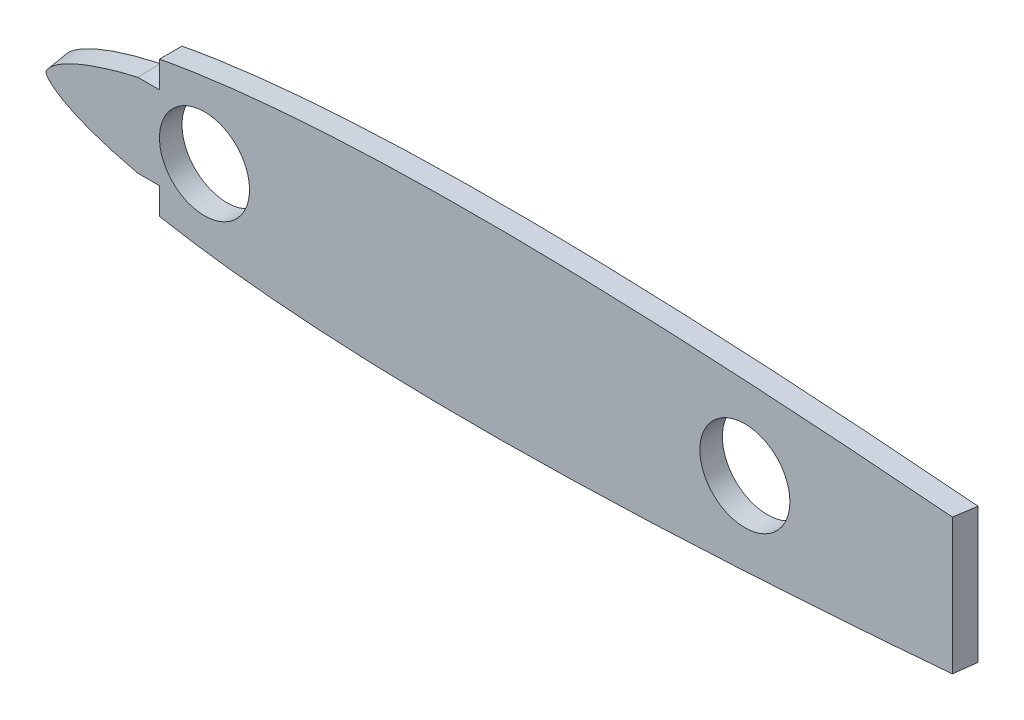
SolidWorks part; units mm, degrees
material "Balsa"
ref_plane "Front Plane" through (0, 0, 0) normal (0, 0, 1) x (1, 0, 0)
ref_plane "Top Plane" through (0, 0, 0) normal (0, 1, 0) x (1, 0, 0)
ref_plane "Right Plane" through (0, 0, 0) normal (1, 0, 0) x (0, 0, -1)
curve "Curve6"
  spline degree 3 poles (214.2507, -0.3619, 0) (214.2507, 0.3619, 0) (213.529, 0.2735, 0) (212.6145, 0.5309, 0) (210.9374, 0.6901, 0) (208.6782, 1.0315, 0) (205.7679, 1.4126, 0) (202.2583, 1.8823, 0) (198.1585, 2.4132, 0) (193.4982, 3.0043, 0) (188.3046, 3.6452, 0) (182.6103, 4.3273, 0) (176.4501, 5.042, 0) (169.8621, 5.7798, 0) (162.8869, 6.5315, 0) (155.5675, 7.2878, 0) (147.9491, 8.039, 0) (140.0787, 8.7745, 0) (132.0046, 9.4847, 0) (123.7769, 10.1577, 0) (115.4459, 10.7824, 0) (107.0633, 11.3474, 0) (98.6805, 11.8408, 0) (90.3493, 12.2502, 0) (82.1211, 12.5645, 0) (74.0464, 12.7737, 0) (66.175, 12.8673, 0) (58.5554, 12.8381, 0) (51.2345, 12.6804, 0) (44.2574, 12.3902, 0) (37.667, 11.9666, 0) (31.5038, 11.4111, 0) (25.8056, 10.7279, 0) (20.6071, 9.9229, 0) (15.9397, 9.0044, 0) (11.8309, 7.9828, 0) (8.304, 6.8681, 0) (5.3769, 5.6708, 0) (3.0589, 4.3988, 0) (1.3536, 3.0497, 0) (0.2614, 1.5908, 0) (-0.1218, 0, 0) (0.2614, -1.5908, 0) (1.3536, -3.0497, 0) (3.0589, -4.3988, 0) (5.3769, -5.6708, 0) (8.304, -6.8681, 0) (11.8309, -7.9828, 0) (15.9397, -9.0044, 0) (20.6071, -9.9229, 0) (25.8056, -10.7279, 0) (31.5038, -11.4111, 0) (37.667, -11.9666, 0) (44.2574, -12.3902, 0) (51.2345, -12.6804, 0) (58.5554, -12.8381, 0) (66.175, -12.8673, 0) (74.0464, -12.7737, 0) (82.1211, -12.5645, 0) (90.3493, -12.2502, 0) (98.6805, -11.8408, 0) (107.0633, -11.3474, 0) (115.4459, -10.7824, 0) (123.7769, -10.1577, 0) (132.0046, -9.4847, 0) (140.0787, -8.7745, 0) (147.9491, -8.039, 0) (155.5675, -7.2878, 0) (162.8869, -6.5315, 0) (169.8621, -5.7798, 0) (176.4501, -5.042, 0) (182.6103, -4.3273, 0) (188.3046, -3.6452, 0) (193.4982, -3.0043, 0) (198.1585, -2.4132, 0) (202.2583, -1.8823, 0) (205.7679, -1.4126, 0) (208.6782, -1.0315, 0) (210.9374, -0.6901, 0) (212.6145, -0.5309, 0) (213.529, -0.2735, 0) (214.2507, -0.3619, 0) (214.2507, 0.3619, 0) (213.529, 0.2735, 0) knots -0.004279 -0.001997 -0.001234 0 0.000762 0.003045 0.006832 0.012101 0.018818 0.026939 0.036415 0.047185 0.05918 0.072328 0.086544 0.101741 0.117823 0.134691 0.15224 0.170361 0.188941 0.207865 0.227016 0.246276 0.265525 0.284645 0.30352 0.322035 0.340078 0.357543 0.374325 0.39033 0.405464 0.419644 0.432793 0.444844 0.455738 0.465429 0.473886 0.481102 0.487102 0.491975 0.495931 0.499383 0.502835 0.50679 0.511664 0.517664 0.524879 0.533337 0.543028 0.553922 0.565972 0.579122 0.593302 0.608436 0.62444 0.641223 0.658687 0.676731 0.695245 0.714121 0.733241 0.75249 0.77175 0.7909 0.809825 0.828404 0.846525 0.864074 0.880942 0.897025 0.912222 0.926438 0.939585 0.951581 0.962351 0.971826 0.979948 0.986664 0.991933 0.995721 0.998003 0.998766 1 1.000762 1.003045 1.006832 periodic
sketch "Sketch1" plane through (0, 0, 0) normal (0, 0, 1) x (1, 0, 0)
  spline S0 degree 3 poles (214.2507, -0.3619) (214.2507, 0.3619) (213.529, 0.2735) (212.6145, 0.5309) (210.9374, 0.6901) (208.6782, 1.0315) (205.7679, 1.4126) (202.2583, 1.8823) (198.1585, 2.4132) (193.4982, 3.0043) (188.3046, 3.6452) (182.6103, 4.3273) (176.4501, 5.042) (169.8621, 5.7798) (162.8869, 6.5315) (155.5675, 7.2878) (147.9491, 8.039) (140.0787, 8.7745) (132.0046, 9.4847) (123.7769, 10.1577) (115.4459, 10.7824) (107.0633, 11.3474) (98.6805, 11.8408) (90.3493, 12.2502) (82.1211, 12.5645) (74.0464, 12.7737) (66.175, 12.8673) (58.5554, 12.8381) (51.2345, 12.6804) (44.2574, 12.3902) (37.667, 11.9666) (31.5038, 11.4111) (25.8056, 10.7279) (20.6071, 9.9229) (15.9397, 9.0044) (11.8309, 7.9828) (8.304, 6.8681) (5.3769, 5.6708) (3.0589, 4.3988) (1.3536, 3.0497) (0.2614, 1.5908) (-0.1218, 0) (0.2614, -1.5908) (1.3536, -3.0497) (3.0589, -4.3988) (5.3769, -5.6708) (8.304, -6.8681) (11.8309, -7.9828) (15.9397, -9.0044) (20.6071, -9.9229) (25.8056, -10.7279) (31.5038, -11.4111) (37.667, -11.9666) (44.2574, -12.3902) (51.2345, -12.6804) (58.5554, -12.8381) (66.175, -12.8673) (74.0464, -12.7737) (82.1211, -12.5645) (90.3493, -12.2502) (98.6805, -11.8408) (107.0633, -11.3474) (115.4459, -10.7824) (123.7769, -10.1577) (132.0046, -9.4847) (140.0787, -8.7745) (147.9491, -8.039) (155.5675, -7.2878) (162.8869, -6.5315) (169.8621, -5.7798) (176.4501, -5.042) (182.6103, -4.3273) (188.3046, -3.6452) (193.4982, -3.0043) (198.1585, -2.4132) (202.2583, -1.8823) (205.7679, -1.4126) (208.6782, -1.0315) (210.9374, -0.6901) (212.6145, -0.5309) (213.529, -0.2735) (214.2507, -0.3619) (214.2507, 0.3619) (213.529, 0.2735) knots -0.004279 -0.001997 -0.001234 0 0.000762 0.003045 0.006832 0.012101 0.018818 0.026939 0.036415 0.047185 0.05918 0.072328 0.086544 0.101741 0.117823 0.134691 0.15224 0.170361 0.188941 0.207865 0.227016 0.246276 0.265525 0.284645 0.30352 0.322035 0.340078 0.357543 0.374325 0.39033 0.405464 0.419644 0.432793 0.444844 0.455738 0.465429 0.473886 0.481102 0.487102 0.491975 0.495931 0.499383 0.502835 0.50679 0.511664 0.517664 0.524879 0.533337 0.543028 0.553922 0.565972 0.579122 0.593302 0.608436 0.62444 0.641223 0.658687 0.676731 0.695245 0.714121 0.733241 0.75249 0.77175 0.7909 0.809825 0.828404 0.846525 0.864074 0.880942 0.897025 0.912222 0.926438 0.939585 0.951581 0.962351 0.971826 0.979948 0.986664 0.991933 0.995721 0.998003 0.998766 1 1.000762 1.003045 1.006832 only from (214.122, 0.2698) to (214.122, 0.2698) construction
  spline S1 degree 3 poles (214.2507, -0.3619) (214.2507, 0.3619) (213.529, 0.2735) (212.6145, 0.5309) (210.9374, 0.6901) (208.6782, 1.0315) (205.7679, 1.4126) (202.2583, 1.8823) (198.1585, 2.4132) (193.4982, 3.0043) (188.3046, 3.6452) (182.6103, 4.3273) (176.4501, 5.042) (169.8621, 5.7798) (162.8869, 6.5315) (155.5675, 7.2878) (147.9491, 8.039) (140.0787, 8.7745) (132.0046, 9.4847) (123.7769, 10.1577) (115.4459, 10.7824) (107.0633, 11.3474) (98.6805, 11.8408) (90.3493, 12.2502) (82.1211, 12.5645) (74.0464, 12.7737) (66.175, 12.8673) (58.5554, 12.8381) (51.2345, 12.6804) (44.2574, 12.3902) (37.667, 11.9666) (31.5038, 11.4111) (25.8056, 10.7279) (20.6071, 9.9229) (15.9397, 9.0044) (11.8309, 7.9828) (8.304, 6.8681) (5.3769, 5.6708) (3.0589, 4.3988) (1.3536, 3.0497) (0.2614, 1.5908) (-0.1218, 0) (0.2614, -1.5908) (1.3536, -3.0497) (3.0589, -4.3988) (5.3769, -5.6708) (8.304, -6.8681) (11.8309, -7.9828) (15.9397, -9.0044) (20.6071, -9.9229) (25.8056, -10.7279) (31.5038, -11.4111) (37.667, -11.9666) (44.2574, -12.3902) (51.2345, -12.6804) (58.5554, -12.8381) (66.175, -12.8673) (74.0464, -12.7737) (82.1211, -12.5645) (90.3493, -12.2502) (98.6805, -11.8408) (107.0633, -11.3474) (115.4459, -10.7824) (123.7769, -10.1577) (132.0046, -9.4847) (140.0787, -8.7745) (147.9491, -8.039) (155.5675, -7.2878) (162.8869, -6.5315) (169.8621, -5.7798) (176.4501, -5.042) (182.6103, -4.3273) (188.3046, -3.6452) (193.4982, -3.0043) (198.1585, -2.4132) (202.2583, -1.8823) (205.7679, -1.4126) (208.6782, -1.0315) (210.9374, -0.6901) (212.6145, -0.5309) (213.529, -0.2735) (214.2507, -0.3619) (214.2507, 0.3619) (213.529, 0.2735) knots -0.004279 -0.001997 -0.001234 0 0.000762 0.003045 0.006832 0.012101 0.018818 0.026939 0.036415 0.047185 0.05918 0.072328 0.086544 0.101741 0.117823 0.134691 0.15224 0.170361 0.188941 0.207865 0.227016 0.246276 0.265525 0.284645 0.30352 0.322035 0.340078 0.357543 0.374325 0.39033 0.405464 0.419644 0.432793 0.444844 0.455738 0.465429 0.473886 0.481102 0.487102 0.491975 0.495931 0.499383 0.502835 0.50679 0.511664 0.517664 0.524879 0.533337 0.543028 0.553922 0.565972 0.579122 0.593302 0.608436 0.62444 0.641223 0.658687 0.676731 0.695245 0.714121 0.733241 0.75249 0.77175 0.7909 0.809825 0.828404 0.846525 0.864074 0.880942 0.897025 0.912222 0.926438 0.939585 0.951581 0.962351 0.971826 0.979948 0.986664 0.991933 0.995721 0.998003 0.998766 1 1.000762 1.003045 1.006832 only from (214.122, 0.2698) to (214.122, 0.2698)
extrude "Boss-Extrude1" add sketch "Sketch1" along normal blind 3.175
sketch "Sketch2" plane through (0, 0, 3.175) normal (0, 0, 1) x (1, 0, 0)
  circle A0 centre (25.4, 0) radius 6.35
  circle A1 centre (101.6, 0) radius 6.35
  dimension "D1" = 12.7
  dimension "D2" = 12.7
  dimension "D3" = 0
  dimension "D4" = 0
  dimension "D5" = 25.4
  dimension "D6" = 101.6
extrude "Cut-Extrude1" cut sketch "Sketch2" against normal through all
sketch "Sketch4" plane through (0, 0, 0) normal (0, 1, 0) x (1, 0, 0)
  line L2 (131.3014, 0) -> (130.8547, -3.175)
  line L4 (214.2185, 0) -> (0, 0) construction
  line L5 (214.2185, 0) -> (131.3014, 0)
  line L6 (214.2185, -3.175) -> (214.2185, 0) construction
  line L7 (214.2185, -3.175) -> (214.2185, 0)
  line L11 (130.8547, -3.175) -> (214.2185, -3.175)
extrude "Cut-Extrude2" cut sketch "Sketch4" against normal through all both and the other way through all contours L5 L2 L11 L7
sketch "Sketch5" plane through (0, 0, 0) normal (0, 0, -1) x (-1, 0, 0)
  line L0 (-19.05, -9.6949) -> (-19.05, -5.9522)
  line L1 (-19.05, -9.6949) -> (-19.05, -5.9522)
  line L2 (-16.002, -5.9522) -> (-19.05, -5.9522)
  line L3 (-16.002, -5.9522) -> (-19.05, -5.9522)
  line L4 (-19.05, 5.9522) -> (-19.05, 9.6949)
  line L5 (-19.05, 5.9522) -> (-19.05, 9.6949)
  line L6 (-19.05, 5.9522) -> (-16.002, 5.9522)
  line L7 (-19.05, 5.9522) -> (-16.002, 5.9522)
  line L8 (-19.05, 9.6949) -> (-19.05, 12.3776)
  line L9 (-19.05, 12.3776) -> (3.9372, 8.6357)
  line L10 (3.9372, 8.6357) -> (2.5117, -11.7446)
  line L11 (2.5117, -11.7446) -> (-19.05, -12.3014)
  line L12 (-19.05, -12.3014) -> (-19.05, -9.6949)
  spline S0 degree 3 poles (1979.4926, 138.2298) (-139.8627, -22.8717) (-64.1253, 18.5865) (-12.6489, 5.1346) (-11.5484, 4.8257) (-10.4651, 4.4981) (-9.3996, 4.1488) (-8.3537, 3.7753) (-7.5049, 3.4422) (-6.8429, 3.1616) (-6.1948, 2.871) (-5.4147, 2.488) (-4.6839, 2.0746) (-4.1514, 1.7348) (-3.7822, 1.4766) (-3.4495, 1.2179) (-3.1565, 0.9593) (-2.9074, 0.7021) (-2.7169, 0.4734) (-2.62, 0.3293) (-2.5683, 0.2322) (-2.5397, 0.1664) (-2.5186, 0.105) (-2.5054, 0.0553) (-2.4997, 0.023) (-2.4987, 0) (-2.4997, -0.023) (-2.5054, -0.0553) (-2.5186, -0.105) (-2.5397, -0.1664) (-2.5683, -0.2322) (-2.62, -0.3293) (-2.7169, -0.4734) (-2.9074, -0.7021) (-3.1565, -0.9593) (-3.4496, -1.2179) (-3.7821, -1.4766) (-4.1514, -1.7348) (-4.6837, -2.0745) (-5.4148, -2.4881) (-6.1948, -2.871) (-6.8429, -3.1616) (-7.5049, -3.4422) (-8.3537, -3.7753) (-9.3996, -4.1488) (-10.4651, -4.4981) (-11.5484, -4.8257) (-12.649, -5.1346) (-63.4171, -18.4015) (-138.5465, 21.5522) (1981.2096, -108.9254) knots -4.215654 -4.215654 -4.215654 -4.215654 0.0625 0.09375 0.125 0.15625 0.1875 0.21875 0.25 0.265625 0.28125 0.3125 0.34375 0.359375 0.375 0.390625 0.40625 0.421875 0.4375 0.453125 0.460938 0.46875 0.476562 0.484375 0.492188 0.5 0.507812 0.515625 0.523438 0.53125 0.539062 0.546875 0.5625 0.578125 0.59375 0.609375 0.625 0.640625 0.65625 0.6875 0.71875 0.734375 0.75 0.78125 0.8125 0.84375 0.875 0.90625 0.9375 5.15664 5.15664 5.15664 5.15664 only from (-16.002, 5.9522) to (-16.002, -5.9522)
  spline S1 degree 3 poles (-16.002, 5.9522) (-15.2548, 5.7866) (-14.1313, 5.522) (-12.6489, 5.1346) (-11.5484, 4.8257) (-10.4651, 4.4981) (-9.3996, 4.1488) (-8.3537, 3.7753) (-7.5049, 3.4422) (-6.8429, 3.1616) (-6.1948, 2.871) (-5.4147, 2.488) (-4.6839, 2.0746) (-4.1514, 1.7348) (-3.7822, 1.4766) (-3.4495, 1.2179) (-3.1565, 0.9593) (-2.9074, 0.7021) (-2.7169, 0.4734) (-2.62, 0.3293) (-2.5683, 0.2322) (-2.5397, 0.1664) (-2.5186, 0.105) (-2.5054, 0.0553) (-2.4997, 0.023) (-2.4987, 0) (-2.4997, -0.023) (-2.5054, -0.0553) (-2.5186, -0.105) (-2.5397, -0.1664) (-2.5683, -0.2322) (-2.62, -0.3293) (-2.7169, -0.4734) (-2.9074, -0.7021) (-3.1565, -0.9593) (-3.4496, -1.2179) (-3.7821, -1.4766) (-4.1514, -1.7348) (-4.6837, -2.0745) (-5.4148, -2.4881) (-6.1948, -2.871) (-6.8429, -3.1616) (-7.5049, -3.4422) (-8.3537, -3.7753) (-9.3996, -4.1488) (-10.4651, -4.4981) (-11.5484, -4.8257) (-12.649, -5.1346) (-14.1311, -5.5219) (-15.2548, -5.7866) (-16.002, -5.9522) knots 0 0 0 0 0.0625 0.09375 0.125 0.15625 0.1875 0.21875 0.25 0.265625 0.28125 0.3125 0.34375 0.359375 0.375 0.390625 0.40625 0.421875 0.4375 0.453125 0.460938 0.46875 0.476562 0.484375 0.492188 0.5 0.507812 0.515625 0.523438 0.53125 0.539062 0.546875 0.5625 0.578125 0.59375 0.609375 0.625 0.640625 0.65625 0.6875 0.71875 0.734375 0.75 0.78125 0.8125 0.84375 0.875 0.90625 0.9375 1 1 1 1
sketch "Sketch6" plane through (0, 0, 3.175) normal (0, 0, 1) x (1, 0, 0)
  line L0 (19.05, -5.8564) -> (19.05, -9.6045)
  line L1 (19.05, -5.8564) -> (19.05, -9.6045)
  line L2 (16.002, -5.8557) -> (19.05, -5.8564)
  line L3 (16.002, -5.8557) -> (19.05, -5.8564)
  line L4 (19.05, 9.6045) -> (19.05, 5.8564)
  line L5 (19.05, 9.6045) -> (19.05, 5.8564)
  line L6 (16.002, 5.8557) -> (19.05, 5.8564)
  line L7 (16.002, 5.8557) -> (19.05, 5.8564)
  line L8 (19.05, 9.6045) -> (19.05, 13.4998)
  line L9 (19.05, 13.4998) -> (-7.4002, 8.6709)
  line L10 (-7.4002, 8.6709) -> (-3.1768, -18.7418)
  line L11 (-3.1768, -18.7418) -> (19.05, -13.4967)
  line L12 (19.05, -13.4967) -> (19.05, -9.6045)
  spline S0 degree 3 poles (-1980.2608, 125.8125) (136.4057, -21.708) (62.4805, 18.4549) (12.7578, 5.0379) (11.6937, 4.7298) (10.6467, 4.4033) (9.6177, 4.0558) (8.6083, 3.6846) (7.6262, 3.2879) (6.6786, 2.8637) (5.7792, 2.4089) (5.0789, 2.0005) (4.5709, 1.6655) (4.2202, 1.4115) (3.9059, 1.1576) (3.6312, 0.9047) (3.3999, 0.6539) (3.2267, 0.4331) (3.1267, 0.2697) (3.0755, 0.1444) (3.0492, 0.0377) (3.0474, 0) (3.0492, -0.0377) (3.0755, -0.1444) (3.1267, -0.2697) (3.2267, -0.4331) (3.3999, -0.6539) (3.6312, -0.9046) (3.9059, -1.1577) (4.2201, -1.4115) (4.571, -1.6655) (5.0788, -2.0004) (5.7793, -2.409) (6.6785, -2.8637) (7.6262, -3.2879) (8.6083, -3.6846) (9.6177, -4.0558) (10.6467, -4.4033) (11.6936, -4.7298) (12.7579, -5.0379) (61.7896, -18.2686) (135.1259, 20.4118) (-1981.8383, -96.8635) knots -4.20929 -4.20929 -4.20929 -4.20929 0.0625 0.09375 0.125 0.15625 0.1875 0.21875 0.25 0.28125 0.3125 0.34375 0.359375 0.375 0.390625 0.40625 0.421875 0.4375 0.453125 0.46875 0.484375 0.5 0.515625 0.53125 0.546875 0.5625 0.578125 0.59375 0.609375 0.625 0.640625 0.65625 0.6875 0.71875 0.75 0.78125 0.8125 0.84375 0.875 0.90625 0.9375 5.149795 5.149795 5.149795 5.149795 only from (16.002, 5.8557) to (16.002, -5.8557)
  spline S1 degree 3 poles (16.002, 5.8557) (15.279, 5.6897) (14.1918, 5.4249) (12.7578, 5.0379) (11.6937, 4.7298) (10.6467, 4.4033) (9.6177, 4.0558) (8.6083, 3.6846) (7.6262, 3.2879) (6.6786, 2.8637) (5.7792, 2.4089) (5.0789, 2.0005) (4.5709, 1.6655) (4.2202, 1.4115) (3.9059, 1.1576) (3.6312, 0.9047) (3.3999, 0.6539) (3.2267, 0.4331) (3.1267, 0.2697) (3.0755, 0.1444) (3.0492, 0.0377) (3.0474, 0) (3.0492, -0.0377) (3.0755, -0.1444) (3.1267, -0.2697) (3.2267, -0.4331) (3.3999, -0.6539) (3.6312, -0.9046) (3.9059, -1.1577) (4.2201, -1.4115) (4.571, -1.6655) (5.0788, -2.0004) (5.7793, -2.409) (6.6785, -2.8637) (7.6262, -3.2879) (8.6083, -3.6846) (9.6177, -4.0558) (10.6467, -4.4033) (11.6936, -4.7298) (12.7579, -5.0379) (14.1916, -5.4248) (15.279, -5.6897) (16.002, -5.8557) knots 0 0 0 0 0.0625 0.09375 0.125 0.15625 0.1875 0.21875 0.25 0.28125 0.3125 0.34375 0.359375 0.375 0.390625 0.40625 0.421875 0.4375 0.453125 0.46875 0.484375 0.5 0.515625 0.53125 0.546875 0.5625 0.578125 0.59375 0.609375 0.625 0.640625 0.65625 0.6875 0.71875 0.75 0.78125 0.8125 0.84375 0.875 0.90625 0.9375 1 1 1 1
loft "Cut-Loft1" cut profiles "Sketch6", "Sketch5" connector at (-7.4002, 8.6709, 3.175) connector at (-3.9372, 8.6357, 0)
